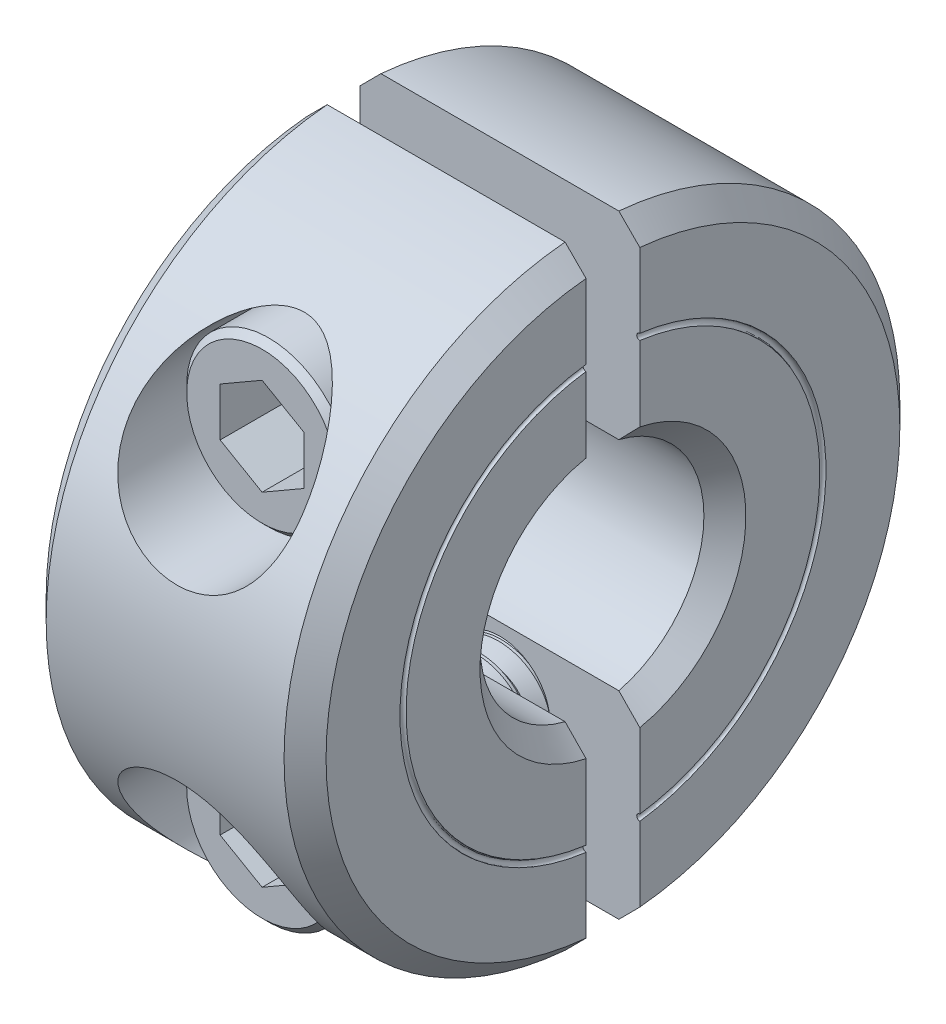
SolidWorks part; units mm, degrees
ref_plane "Front Plane" through (0, 0, 0) normal (0, 0, 1) x (1, 0, 0)
ref_plane "Top Plane" through (0, 0, 0) normal (0, 1, 0) x (1, 0, 0)
ref_plane "Right Plane" through (0, 0, 0) normal (1, 0, 0) x (0, 0, -1)
sketch "Sketch1" plane through (0, 0, 0) normal (1, 0, 0) x (0, 0, -1)
  line L0 (-0.762, 8.7312) -> (0.762, 8.7312) construction
  line L1 (0.762, 8.7312) -> (0.762, -8.6979) construction
  line L2 (-0.762, 8.7312) -> (-0.762, -8.6979) construction
  line L3 (-8.7313, 4.8514) -> (8.7313, 4.8514) construction
  line L4 (8.7313, 4.8514) -> (8.7313, 6.2738) construction
  line L5 (8.7313, 6.2738) -> (-3.1918, 6.2738) construction
  line L6 (-3.1918, 6.2738) -> (-3.1918, 7.1755) construction
  line L7 (-5.7948, 7.1755) -> (-3.1918, 7.1755) construction
  line L8 (-8.7313, 7.3025) -> (-8.7313, 4.8514) construction
  line L9 (-5.9807, 4.8514) -> (-5.9807, 7.1755) construction
  line L10 (2.9201, 6.2738) -> (2.9201, 4.8514) construction
  line L11 (2.8804, 6.3425) -> (3.1979, 5.7926) construction
  line L16 (3.1979, 5.7926) -> (3.5154, 6.3425) construction
  line L17 (3.5154, 6.3425) -> (2.8804, 6.3425) construction
  line L18 (3.1979, 6.3425) -> (3.1979, 6.2738) construction
  line L19 (2.9201, 6.2738) -> (3.4757, 6.2738) construction
  line L20 (3.1979, 6.3082) -> (3.4955, 6.3082) construction
  line L21 (3.1979, 6.3082) -> (2.9002, 6.3082) construction
  line L22 (3.1979, 5.7926) -> (3.1979, 5.8614) construction
  line L23 (3.1582, 5.8614) -> (3.2376, 5.8614) construction
  line L24 (2.4438, 6.2738) -> (2.9201, 5.7976) construction
  line L25 (-5.9807, 6.9896) -> (-5.7948, 7.1755) construction
  line L26 (-8.7313, 7.3025) -> (-3.1918, 7.3025) construction
  line L27 (-3.1918, 7.3025) -> (-3.1918, 7.1755) construction
  line L28 (-7.2594, -4.8514) -> (7.2594, -4.8514) construction
  line L29 (0, 0) -> (-3.175, 0) construction
  line L30 (-3.1918, 2.5273) -> (-1.9218, 2.5273) construction
  circle A0 centre (0, 0) radius 3.175 construction
  circle A1 centre (0, 0) radius 8.7312 construction
  point P8 (0, 8.7312)
  point P12 (8.7313, 0)
  point P13 (-8.7313, 0)
  point P45 (1.8882, 6.2738)
  point P47 (8.7313, 3.429)
  point P48 (-3.1918, 6.2738)
  point P49 (0, -4.8514)
  point P50 (0, 3.175)
  point P51 (0, 4.8514)
  point P52 (-3.1918, 2.5273)
  dimension "For Shaft Diameter" = 6.35
  dimension "OD" = 17.4625
  dimension "Separation" = 1.524
  dimension "Thread Diameter" = 2.8448
  dimension "Head Height" = 2.7889
  dimension "D2" = 6.1119
  dimension "Thread Pitch" = 0.635
  dimension "D3" = 0.0794
  dimension "D4" = 45
  dimension "D5" = 0.4763
  dimension "D6" = 0.1859
  dimension "Head Diameter" = 4.6482
  dimension "D7" = 0.127
  dimension "D9" = 5.08
  dimension "D8" = 0.254
  dimension "D1" = 1.27
sketch "Sketch2" plane through (0, 0, 0) normal (0, 0, 1) x (1, 0, 0)
  line L0 (0, -8.7312) -> (0, 8.7312) construction
  line L1 (0, -8.7312) -> (0, 8.7312) construction
  line L2 (-3.9688, 0) -> (3.9688, 0) construction
  line L3 (3.9688, 0) -> (3.9688, 8.7312) construction
  line L4 (3.9688, 8.7312) -> (0, 8.7312) construction
  line L5 (0, -3.175) -> (0, 3.175) construction
  line L6 (0, -3.175) -> (0, 3.175) construction
  line L7 (0, 8.7312) -> (0, 3.175) construction
  line L8 (3.9688, 6.0404) -> (3.9688, 5.8658) construction
  line L10 (0, 6.2262) -> (-1.1906, 5.5388) construction
  line L11 (-1.1906, 5.5388) -> (-1.1906, 4.164) construction
  line L12 (-1.1906, 4.164) -> (0, 3.4766) construction
  line L13 (0, 3.4766) -> (1.1906, 4.164) construction
  line L14 (1.1906, 4.164) -> (1.1906, 5.5388) construction
  line L15 (1.1906, 5.5388) -> (0, 6.2262) construction
  arc A0 (3.9688, 6.0404) -> (3.9688, 5.8658) centre (3.9688, 5.9531) ccw construction
  circle A1 centre (0, 4.8514) radius 1.1906 construction
  circle A2 centre (0, -4.8514) radius 2.3241 construction
  point P2 (0, 4.8514)
  point P4 (0, 0)
  point P9 (0, 0)
  point P15 (0, 5.9531)
  point P16 (-3.9688, 0)
  point P18 (3.9688, 0)
  point P19 (0, -4.8514)
  point P30 (0, -7.1755)
  dimension "D1" = 0.0873
  dimension "D2" = 4.6482
  dimension "Width" = 7.9375
  dimension "Hex" = 2.3813
ref_plane "Plane1" through (0, 0, 3.1918) normal (0, 0, 1) x (1, 0, 0)
ref_plane "Plane2" through (0, 0, -2.9201) normal (0, 0, 1) x (1, 0, 0)
sketch "Sketch3" plane through (0, 0, 0) normal (1, 0, 0) x (0, 0, -1)
  line L0 (0.762, 8.7312) -> (0.762, -8.6979) construction
  line L1 (-0.762, 8.7312) -> (-0.762, -8.6979) construction
  line L2 (0.762, 8.7312) -> (0.762, 3.0822)
  line L3 (-0.762, 8.7312) -> (-0.762, 3.0822)
  line L4 (-0.762, -3.0822) -> (-0.762, -8.6979)
  line L5 (0.762, -3.0822) -> (0.762, -8.6979)
  circle A0 centre (0, 0) radius 8.7312 construction
  circle A1 centre (0, 0) radius 3.175 construction
  arc A2 (-0.762, 8.6979) -> (-0.762, -8.6979) centre (0, 0) ccw
  arc A3 (0.762, -3.0822) -> (0.762, 3.0822) centre (0, 0) ccw
  arc A4 (0.762, -8.6979) -> (0.762, 8.6979) centre (0, 0) ccw
  arc A5 (-0.762, 3.0822) -> (-0.762, -3.0822) centre (0, 0) ccw
extrude "Boss-Extrude1" add sketch "Sketch3" along normal up to vertex (3.9688 mm away) from vertex contours L5 A4 L2 A3 | A5 L3 A2 L4 region at (0, 0, -4.393) region at (0, 0, 4.393) up to point (3.9688, 0, 0) starting at point (-3.9688, 0, 0)
fillet "Fillet1" radius 0.5953 4 edges at (-3.9688, 0, 3.175) (-3.9688, 0, 8.7312) (3.9688, 0, 3.175) (3.9688, 0, 8.7312) profile chamfer
fillet "Fillet2" radius 0.5953 4 edges at (-3.9688, 0, -8.7312) (-3.9688, 0, -3.175) (3.9688, 0, -3.175) (3.9688, 0, -8.7312) profile chamfer
sketch "Sketch4" plane through (0, 0, 0) normal (0, 0, 1) x (1, 0, 0)
  line L0 (3.9688, 0) -> (3.9688, 8.7312) construction
  line L1 (3.9688, 5.8658) -> (3.9688, 6.0404)
  arc A0 (3.9688, 6.0404) -> (3.9688, 5.8658) centre (3.9688, 5.9531) ccw construction
  arc A1 (3.9688, 6.0404) -> (3.9688, 5.8658) centre (3.9688, 5.9531) ccw
revolve "Cut-Revolve1" cut sketch "Sketch4" angle 360 about L2
sketch "Sketch6" plane through (0, 0, 0) normal (1, 0, 0) x (0, 0, -1)
  line L0 (-8.7313, 4.8514) -> (8.7313, 4.8514)
  line L1 (8.7313, 4.8514) -> (8.7313, 6.2738)
  line L2 (8.7313, 6.2738) -> (-3.1918, 6.2738)
  line L5 (-8.7313, 7.3025) -> (-8.7313, 4.8514)
  line L6 (-8.7313, 7.3025) -> (-3.1918, 7.3025)
  line L7 (-3.1918, 7.3025) -> (-3.1918, 6.2738)
revolve "Cut-Revolve2" cut sketch "Sketch6" angle 360 about L3
sketch "Sketch7" plane through (0, 0, 0) normal (1, 0, 0) x (0, 0, -1)
  line L0 (-3.175, 0) -> (3.175, 0) construction
  line L6 (-8.7313, -7.3025) -> (-8.7313, -4.8514)
  line L7 (-3.1918, -7.3025) -> (-8.7313, -7.3025)
  line L8 (-3.1918, -6.2738) -> (-3.1918, -7.3025)
  line L9 (8.7313, -6.2738) -> (-3.1918, -6.2738)
  line L10 (8.7313, -4.8514) -> (8.7313, -6.2738)
  line L11 (-8.7313, -4.8514) -> (8.7313, -4.8514)
  line L19 (-8.7313, 4.8514) -> (8.7313, 4.8514)
  line L20 (8.7313, 4.8514) -> (8.7313, 6.2738)
  line L21 (8.7313, 6.2738) -> (-3.1918, 6.2738)
  line L22 (-3.1918, 6.2738) -> (-3.1918, 7.3025)
  line L23 (-3.1918, 7.3025) -> (-8.7313, 7.3025)
  line L24 (-8.7313, 7.3025) -> (-8.7313, 4.8514)
  line L25 (-8.7313, 4.8514) -> (8.7313, 4.8514) construction
  line L26 (8.7313, 4.8514) -> (8.7313, 6.2738) construction
  line L27 (8.7313, 6.2738) -> (-3.1918, 6.2738) construction
  line L28 (-3.1918, 6.2738) -> (-3.1918, 7.3025) construction
  line L29 (-3.1918, 7.3025) -> (-8.7313, 7.3025) construction
  line L30 (-8.7313, 7.3025) -> (-8.7313, 4.8514) construction
  circle A0 centre (0, 0) radius 3.175 construction
  dimension "D1" = 0
revolve "Cut-Revolve3" cut sketch "Sketch7" angle 360 about L11
sketch "Sketch8" plane through (0, 0, 0) normal (1, 0, 0) x (0, 0, -1)
  line L0 (-5.9807, 4.8514) -> (-5.9807, 6.9896)
  line L1 (-5.7948, 7.1755) -> (-3.1918, 7.1755)
  line L2 (-3.1918, 7.1755) -> (-3.1918, 6.2738)
  line L3 (-3.1918, 6.2738) -> (2.4438, 6.2738)
  line L4 (2.9201, 5.7976) -> (2.9201, 4.8514)
  line L5 (2.9201, 4.8514) -> (-5.9807, 4.8514)
  line L6 (2.4438, 6.2738) -> (2.9201, 5.7976)
  line L7 (-5.9807, 6.9896) -> (-5.7948, 7.1755)
revolve "Revolve1" add sketch "Sketch8" angle 360 about L3
sketch "Sketch9" plane through (0, 0, 0) normal (0, 0, 1) x (1, 0, 0)
  line L0 (-1.1906, 5.5388) -> (-1.1906, 4.164) construction
  line L1 (-1.1906, 4.164) -> (0, 3.4766) construction
  line L2 (0, 3.4766) -> (1.1906, 4.164) construction
  line L3 (1.1906, 4.164) -> (1.1906, 5.5388) construction
  line L4 (1.1906, 5.5388) -> (0, 6.2262) construction
  line L5 (0, 6.2262) -> (-1.1906, 5.5388) construction
  line L6 (-1.1906, 5.5388) -> (-1.1906, 4.164)
  line L7 (-1.1906, 4.164) -> (0, 3.4766)
  line L8 (0, 3.4766) -> (1.1906, 4.164)
  line L9 (1.1906, 4.164) -> (1.1906, 5.5388)
  line L10 (1.1906, 5.5388) -> (0, 6.2262)
  line L11 (0, 6.2262) -> (-1.1906, 5.5388)
extrude "Cut-Extrude2" cut sketch "Sketch9" against normal blind 2.3813 from vertex starting at point (0, 4.8514, 5.9807)
mirror "Mirror1" about plane through (0, 0, 0) normal (0, 1, 0) of bodies 117
split "Split1" trim tools "Plane1" bodies to split 117 127 resulting bodies 119 120
sketch "Sketch10" plane through (0, 0, -2.9201) normal (0, 0, 1) x (1, 0, 0)
  circle A0 centre (0, 4.8514) radius 1.4224
curve "Helix/Spiral1" pitch 0.635 height 7.0009 radius 1.4224 centre (0, 4.8514, -2.9201) axis (0, 0, 1) start towards (0, 1, 0)
sketch "Sketch11" plane through (0, 0, 0) normal (1, 0, 0) x (0, 0, -1)
  line L0 (2.9002, 6.3082) -> (3.1582, 5.8614)
  line L1 (3.1582, 5.8614) -> (3.2376, 5.8614)
  line L2 (3.2376, 5.8614) -> (3.4955, 6.3082)
  line L3 (3.4955, 6.3082) -> (2.9002, 6.3082)
sweep "Cut-Sweep1" cut profiles "Sketch11" path "Helix/Spiral1" align with end faces yes
combine bodies "Combine1" operation type add bodies to combine 121 119
delete or keep bodies "Body-Delete/Keep 1" bodies 118
pattern_circular "CirPattern3" count 2 over 360 about axis through (0, 0, 0) along (0, 0, 1) of bodies 124
equation "\"D1@Fillet1\"=\"Width@Sketch2\"*.075"
equation "\"D1@Fillet2\"=\"D1@Fillet1\""
equation "\"D3@Sketch1\"=\"Thread Pitch@Sketch1\"/8"
equation "\"D5@Sketch1\"=\"Thread Pitch@Sketch1\"*.75"
equation "\"D1@Cut-Extrude2\"=\"Hex@Sketch2\""
equation "\"D3@Helix/Spiral1\"=\"D2@Sketch1\"+\"Thread Pitch@Sketch1\"+.01"
equation "\"D4@Helix/Spiral1\"=\"Thread Pitch@Sketch1\""
equation "\"Head Height@Sketch1\"=\"Head Diameter@Sketch1\"*.6"
equation "\"D6@Sketch1\"=\"Head Diameter@Sketch1\"*.04"
equation "\"D1@Sketch2\"=\"OD@Sketch1\"*.005"
equation "\"D2@Sketch2\"=\"Head Diameter@Sketch1\""
equation "\"D9@Sketch1\"=\"Thread Pitch@Sketch1\"*8"
equation "\"D2@Sketch1\"=\"OD@Sketch1\"*.35"
